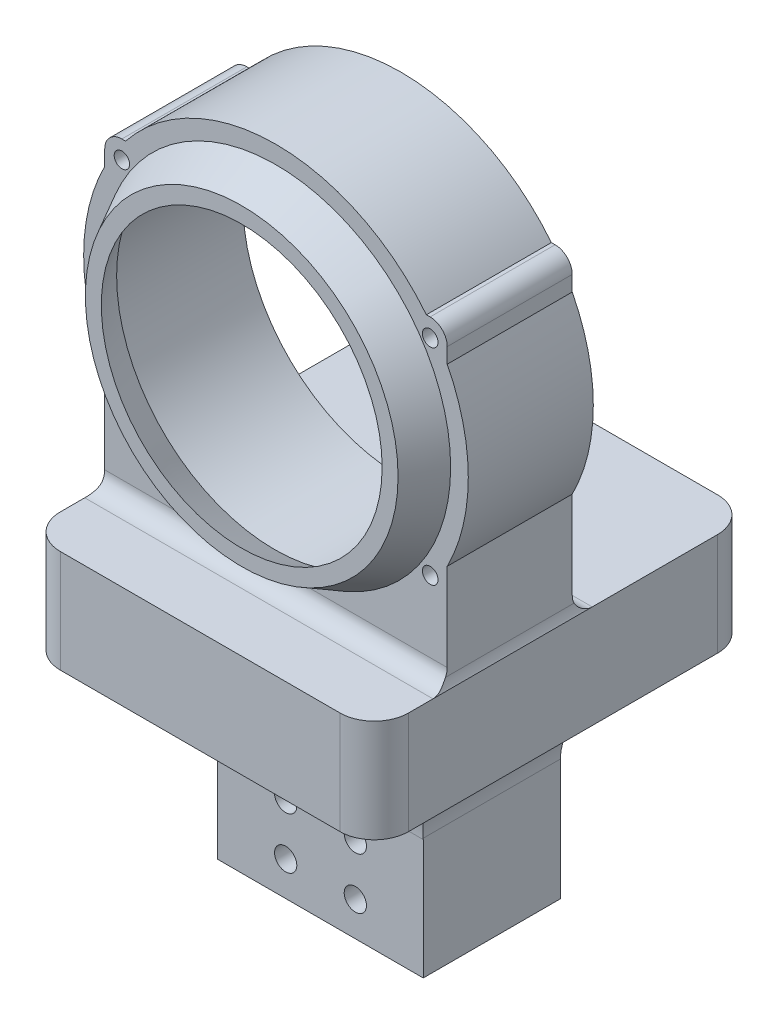
SolidWorks part; units mm, degrees
ref_plane "Alzado" through (0, 0, 0) normal (0, 0, 1) x (1, 0, 0)
ref_plane "Planta" through (0, 0, 0) normal (0, 1, 0) x (1, 0, 0)
ref_plane "Vista lateral" through (0, 0, 0) normal (1, 0, 0) x (0, 0, -1)
sketch "Croquis1" plane through (0, 0, 0) normal (0, 1, 0) x (1, 0, 0)
  line L1 (-50.8381, 55.1406) -> (50.8381, 55.1406)
  line L2 (-50.8381, 55.1406) -> (-50.8381, -55.1406)
  line L3 (-50.8381, -55.1406) -> (50.8381, -55.1406)
  line L4 (50.8381, 55.1406) -> (50.8381, -55.1406)
  line L5 (-50.8381, 55.1406) -> (50.8381, -55.1406) construction
  line L6 (-50.8381, -55.1406) -> (50.8381, 55.1406) construction
extrude "Saliente-Extruir1" add sketch "Croquis1" along normal blind 30
sketch "Croquis3" plane through (0, 0, 0) normal (0, 0, 1) x (1, 0, 0)
  line L0 (43.907, 121.15) -> (45, 121.15)
  line L1 (50, 60.5996) -> (50, 30)
  line L2 (0, 0) -> (0, 85.4991) construction
  line L10 (-45, 121.15) -> (-43.907, 121.15)
  line L11 (-50, 116.15) -> (-50, 111.7004)
  line L12 (-50, 30) -> (50, 30)
  line L13 (50, 116.15) -> (50, 111.7004)
  line L15 (-50, 60.5996) -> (-50, 30)
  circle A0 centre (0, 86.15) radius 46.15
  circle A1 centre (0, 86.15) radius 56.15
  arc A2 (45, 121.15) -> (50, 116.15) centre (45, 116.15) cw
  arc A3 (-45, 121.15) -> (-50, 116.15) centre (-45, 116.15) ccw
  point P5 (-0.8152, 30)
  point P17 (50, 121.15)
  point P20 (-50, 121.15)
  dimension "D4" = 92.3
  dimension "D6" = 5
  dimension "D1" = 100
  dimension "D2" = 10
  dimension "D3" = 35
  dimension "D5" = 50
extrude "Saliente-Extruir2" add sketch "Croquis3" against normal blind 36.5 from offset 33 contours A1 L15 L12 | A1 L12 L1 | L10 A3 L11 A1 | A2 L0 A1 L13 | A1 | A0 region at (47.8302, 117.6386, 0) region at (-47.8302, 117.6386, 0) region at (38.2791, 38.5026, 0) region at (-38.2791, 38.5026, 0)
sketch "Croquis5" plane through (0, 0, 33) normal (0, 0, 1) x (1, 0, 0)
  circle A0 centre (0, 86.15) radius 41
  circle A1 centre (0, 86.15) radius 51
  circle A2 centre (0, 86.15) radius 46.15 construction
  circle A3 centre (0, 86.15) radius 46.15 construction
  dimension "D1" = 82
  dimension "D2" = 10
extrude "Saliente-Extruir3" add sketch "Croquis5" along normal blind 10
chamfer "Chaflán1" distance 10 angle 28.15 1 edges at (41, 86.15, 33) first distance on face at (41, 86.15, 43)
chamfer "Chaflán2" distance 10 angle 28.15 1 edges at (51, 86.15, 43) first distance on face at (51, 86.15, 43)
fillet "Redondeo1" radius 5 4 edges at (0, 30, -3.5) (-50, 30, 14.75) (0, 30, 33) (50, 30, 14.75)
sketch "Croquis7" plane through (0, 0, -3.5) normal (0, 0, -1) x (-1, 0, 0)
  line L0 (0, 85.85) -> (71.2114, 85.85) construction
  circle A0 centre (44.9882, 115.8636) radius 2.2483
  circle A1 centre (-45.0262, 115.8636) radius 2.2831
  circle A2 centre (-45.0262, 55.8364) radius 2.2831
  circle A3 centre (44.9882, 55.8364) radius 2.2483
  dimension "D3" = 4.4965
  dimension "D1" = 30.0136
  dimension "D2" = 44.9882
extrude "Cortar-Extruir2" cut sketch "Croquis7" against normal through all
fillet "Redondeo2" radius 10 4 edges at (-50.8381, 15, -55.1406) (-50.8381, 15, 55.1406) (50.8381, 15, -55.1406) (50.8381, 15, 55.1406)
sketch "Croquis8" plane through (0, 0, 0) normal (0, -1, 0) x (1, 0, 0)
  line L0 (30, 20) -> (30, -20)
  line L1 (-20, 10) -> (20, 10)
  line L2 (-20, 10) -> (-20, -10)
  line L3 (-20, -10) -> (20, -10)
  line L4 (20, 10) -> (20, -10)
  line L5 (-20, 10) -> (20, -10) construction
  line L6 (-20, -10) -> (20, 10) construction
  line L7 (-30, -20) -> (30, -20)
  line L8 (-30, 20) -> (-30, -20)
  line L9 (-30, 20) -> (30, 20)
  point P0 (0, 0)
  dimension "D1" = 20
  dimension "D2" = 40
  dimension "D3" = 10
extrude "Saliente-Extruir4" add sketch "Croquis8" along normal blind 60
fillet "Redondeo3" radius 25 4 edges at (-30, 0, 0) (0, 0, -20) (0, 0, 20) (30, 0, 0)
sketch "Croquis9" plane through (0, 0, -20) normal (0, 0, -1) x (-1, 0, 0)
  line L0 (0, -60) -> (0, -33.4422) construction
  line L1 (30, -60) -> (-30, -60) construction
  line L2 (30, -42.5) -> (-9.4009, -42.5) construction
  line L3 (30, -60) -> (30, -25) construction
  line L4 (-30, -60) -> (-30, -25) construction
  circle A0 centre (-10.17, -50) radius 3.25
  circle A1 centre (10.17, -50) radius 3.25
  circle A2 centre (10.17, -35) radius 3.25
  circle A3 centre (-10.17, -35) radius 3.25
  dimension "D1" = 6.5
  dimension "D2" = 10
  dimension "D3" = 19.83
extrude "Cortar-Extruir3" cut sketch "Croquis9" against normal through all
